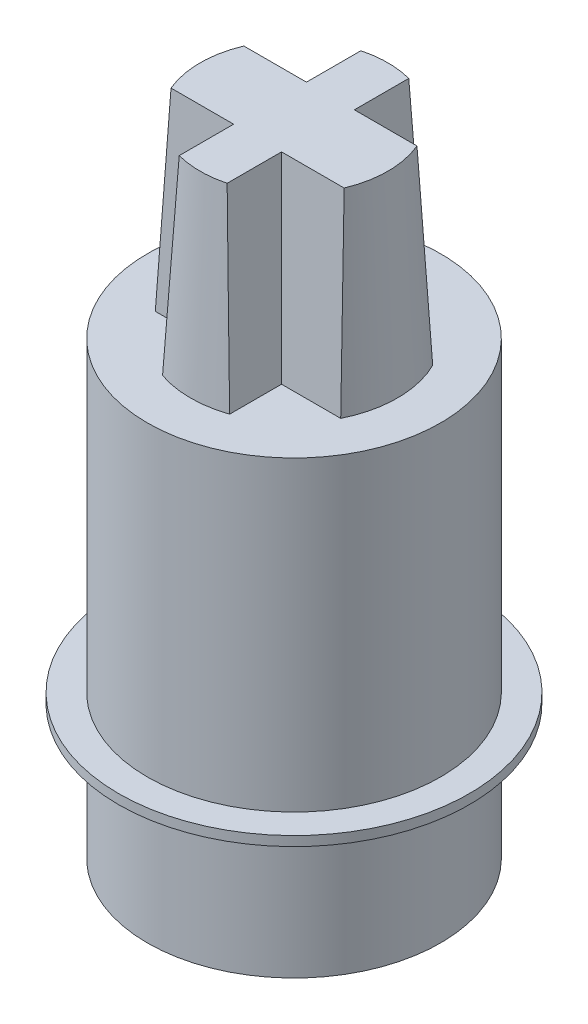
SolidWorks part; units mm, degrees
ref_plane "Спереди" through (0, 0, 0) normal (0, 0, 1) x (1, 0, 0)
ref_plane "Сверху" through (0, 0, 0) normal (0, 1, 0) x (1, 0, 0)
ref_plane "Справа" through (0, 0, 0) normal (1, 0, 0) x (0, 0, -1)
sketch "Эскиз основа" plane through (0, 0, 0) normal (0, 0, 1) x (1, 0, 0)
  line L0 (0, 16.2557) -> (0, 0) construction
  line L1 (0, 0) -> (7.65, 0)
  line L2 (7.65, 0) -> (7.65, 7)
  line L3 (7.65, 7) -> (9.15, 7)
  line L4 (9.15, 7) -> (9.15, 7.5)
  line L7 (0, 0) -> (0, 33.5)
  line L9 (9.15, 7.5) -> (7.65, 7.5)
  line L10 (7.65, 7.5) -> (7.65, 33.5)
  line L11 (7.65, 33.5) -> (0, 33.5)
  dimension "D1" = 7.65
  dimension "D3" = 0.5
  dimension "D4" = 26
  dimension "D5" = 7
  dimension "D6" = 1.5
revolve "Вал заготовка" add sketch "Эскиз основа" angle 360 about L0
sketch "Эскиз пазов под резистор" plane through (0, 33.5, 0) normal (0, 1, 0) x (1, 0, 0)
  line L0 (0, 5.4) -> (0, -5.4) construction
  line L1 (-7.65, 0) -> (7.65, 0) construction
  line L5 (-1.75, 2.4) -> (1.75, 2.4)
  line L10 (-1.75, 2.4) -> (-1.75, -2.4)
  line L11 (1.75, 2.4) -> (1.75, -2.4)
  line L14 (-1.75, -2.4) -> (1.75, -2.4)
  line L18 (-1.75, 2.4) -> (-1.75, 5.1086)
  line L19 (-1.75, 2.4) -> (-4.8374, 2.4)
  line L20 (1.75, 2.4) -> (4.8374, 2.4)
  line L21 (1.75, 2.4) -> (1.75, 5.1086)
  line L22 (1.75, -2.4) -> (4.8374, -2.4)
  line L23 (1.75, -2.4) -> (1.75, -5.1086)
  line L24 (-1.75, -2.4) -> (-4.8374, -2.4)
  line L25 (-1.75, -2.4) -> (-1.75, -5.1086)
  circle A0 centre (0, 0) radius 7.65 construction
  circle A1 centre (0, 0) radius 7.65 construction
  circle A2 centre (0, 0) radius 3.25
  circle A7 centre (0, 0) radius 5.4
  point P21 (-1.75, 0)
  point P22 (0, 2.4)
  dimension "D1" = 6.5
  dimension "D2" = 3.5
  dimension "D7" = 10.8
  dimension "D5" = 4.8
extrude "Пазы для крепления резистора" cut sketch "Эскиз пазов под резистор" against normal blind 10
chamfer "Фаска1" distance 0.5 distance2 10 12 edges at (-3.2937, 33.5, -2.4) (-5.4, 33.5, 0) (-3.2937, 33.5, 2.4) (-1.75, 33.5, 3.7543) (0, 33.5, 5.4) (1.75, 33.5, 3.7543) (3.2937, 33.5, 2.4) (5.4, 33.5, 0) (3.2937, 33.5, -2.4) (1.75, 33.5, -3.7543) (0, 33.5, -5.4) (-1.75, 33.5, -3.7543)
